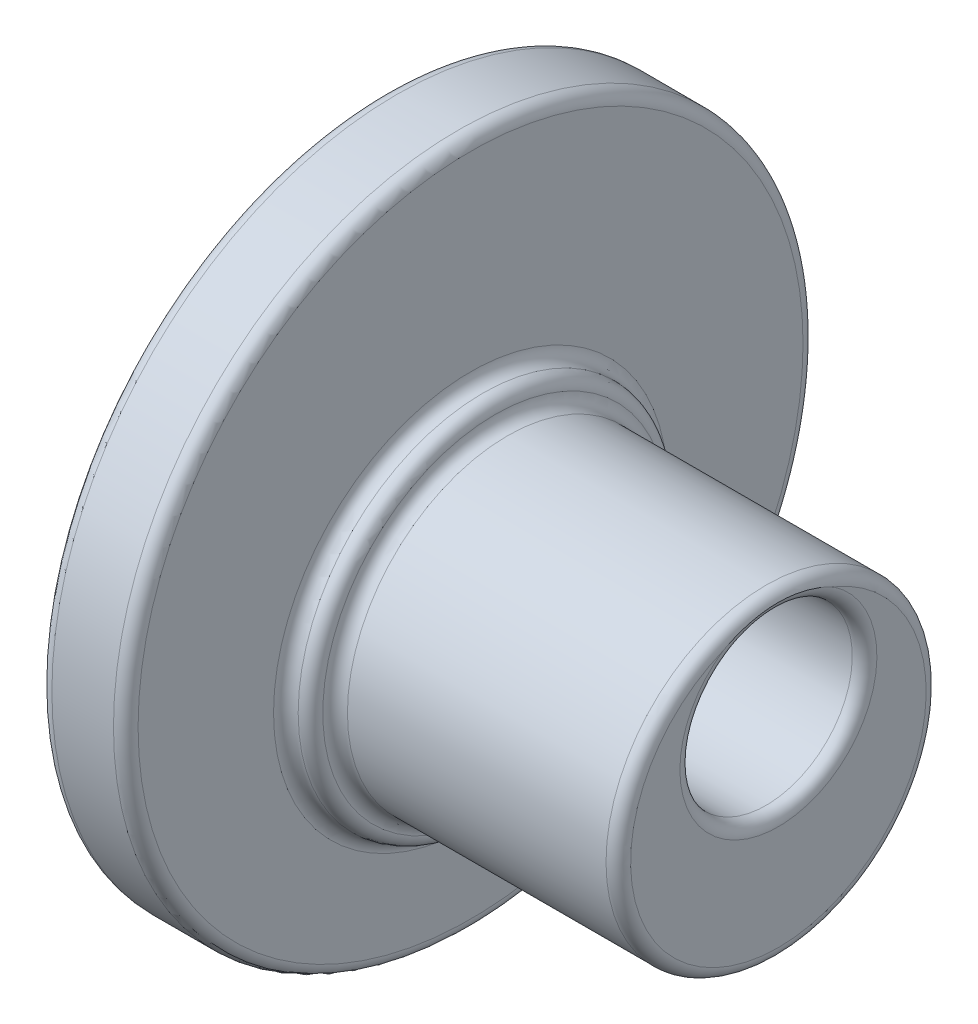
SolidWorks part; units mm, degrees
ref_plane "Plan de face" through (0, 0, 0) normal (0, 0, 1) x (1, 0, 0)
ref_plane "Plan de dessus" through (0, 0, 0) normal (0, 1, 0) x (1, 0, 0)
ref_plane "Plan de droite" through (0, 0, 0) normal (1, 0, 0) x (0, 0, -1)
sketch "Esquisse1" plane through (0, 0, 0) normal (0, 0, 1) x (1, 0, 0)
  line L0 (0, 0) -> (108.1761, 0) construction
  line L1 (0, 0) -> (0, 56)
  line L5 (0, 56) -> (14, 56)
  line L6 (14, 56) -> (14, 0)
  line L7 (0, 0) -> (14, 0)
  dimension "D1" = 56
  dimension "D2" = 14
revolve "Révolution1" add sketch "Esquisse1" angle 360 about L0
sketch "Esquisse2" plane through (0, 0, 0) normal (-1, 0, 0) x (0, 0, 1)
  circle A0 centre (0, 0) radius 24.5
  circle A3 centre (0, 0) radius 56 construction
  dimension "D1" = 49
extrude "Enlèv. mat.-Extru.1" cut sketch "Esquisse2" against normal blind 10
sketch "Esquisse3" plane through (0, 0, 0) normal (0, 0, 1) x (1, 0, 0)
  line L0 (58.5999, -9) -> (-9.8795, -9) construction
  line L1 (14, 21) -> (18, 21)
  line L2 (14, -56) -> (14, 56) construction
  line L3 (18, 21) -> (18, 17)
  line L4 (18, 17) -> (60, 17)
  line L8 (60, 17) -> (64, 17)
  line L9 (64, 17) -> (64, -9)
  line L10 (64, -9) -> (14, -9)
  line L11 (14, -9) -> (14, 21)
  dimension "D1" = 9
  dimension "D2" = 30
  dimension "D3" = 4
  dimension "D4" = 4
  dimension "D5" = 42
  dimension "D9" = 4
revolve "Révolution2" add sketch "Esquisse3" angle 360 about L0
sketch "Esquisse4" plane through (10, 0, 0) normal (-1, 0, 0) x (0, 0, 1)
  circle A0 centre (0, 0) radius 14
  dimension "D1" = 28
extrude "Enlèv. mat.-Extru.2" cut sketch "Esquisse4" against normal through all
fillet "Congé1" radius 2 10 edges at (64, 0, 14) (64, 17, 0) (18, 17, 0) (18, 21, 0) (14, 21, 0) (14, 0, 56) (10, 0, 14) (10, 0, 24.5) (0, 0, 56) (0, 0, 24.5)
